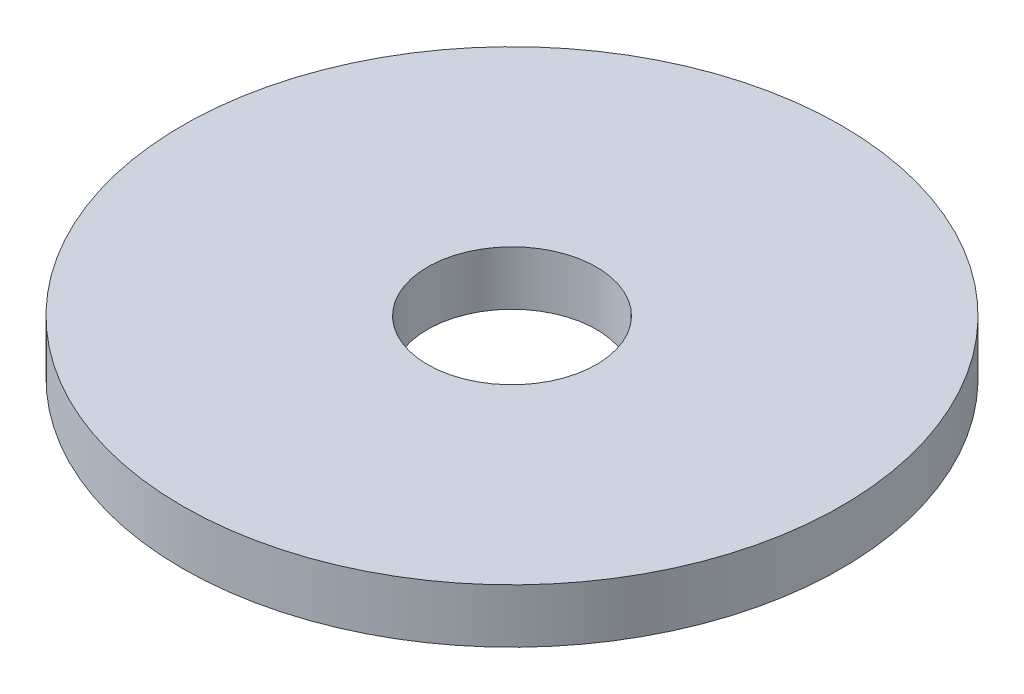
SolidWorks part; units mm, degrees
ref_plane "Front Plane" through (0, 0, 0) normal (0, 0, 1) x (1, 0, 0)
ref_plane "Top Plane" through (0, 0, 0) normal (0, 1, 0) x (1, 0, 0)
ref_plane "Right Plane" through (0, 0, 0) normal (1, 0, 0) x (0, 0, -1)
sketch "Sketch1" plane through (0, 0, 0) normal (0, 1, 0) x (1, 0, 0)
  circle A0 centre (0, 0) radius 97.5
  dimension "FLANGE_OD" = 195
extrude "Boss-Extrude1" add sketch "Sketch1" along normal blind 16
sketch "Sketch2" plane through (0, 0, 0) normal (0, 1, 0) x (1, 0, 0)
  circle A0 centre (0, 0) radius 25
  dimension "BORE_D" = 50
extrude "Cut-Extrude1" cut sketch "Sketch2" along normal through all
sketch "Sketch3" plane through (0, 16, 0) normal (0, 1, 0) x (1, 0, 0)
  circle A0 centre (0, 0) radius 16.1503 construction
  circle A1 centre (-16.1503, 0) radius 4.6687
  dimension "BOLT_D" = 9.3374
  dimension "BOLT_PCD" = 32.3006
extrude "Cut-Extrude2" cut sketch "Sketch3" against normal blind 10.6509 rebuild error yes
pattern_circular "CirPattern1" count 3 over 360 rebuild error yes
